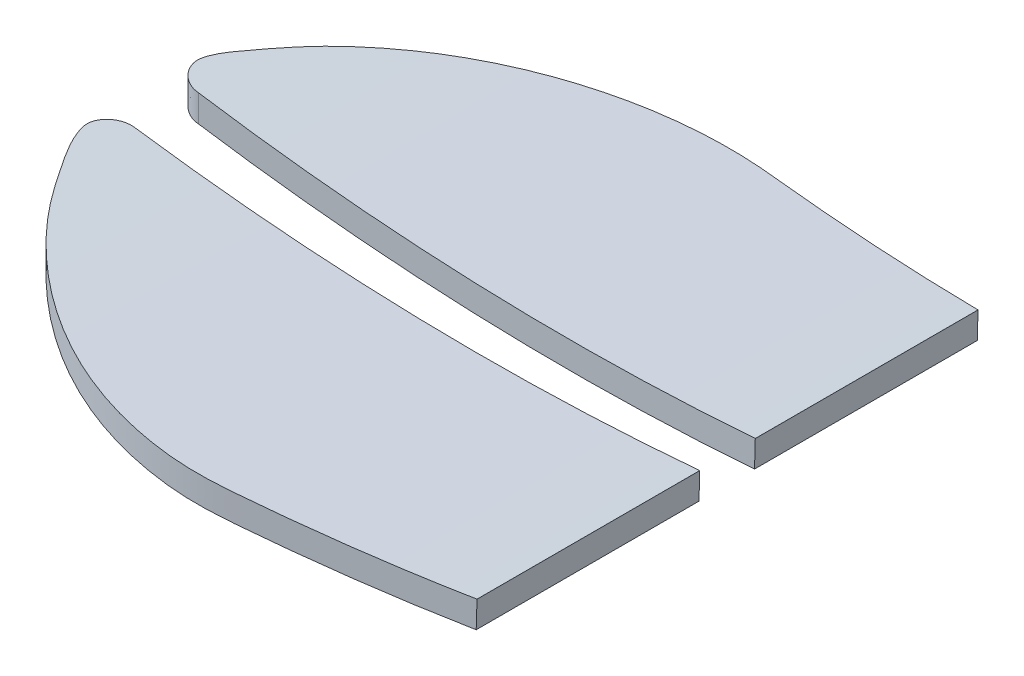
SolidWorks part; units mm, degrees
material "BUTİL"
ref_plane "Ön Düzlem" through (0, 0, 0) normal (0, 0, 1) x (1, 0, 0)
ref_plane "Üst Düzlem" through (0, 0, 0) normal (0, 1, 0) x (1, 0, 0)
ref_plane "Sağ Düzlem" through (0, 0, 0) normal (1, 0, 0) x (0, 0, -1)
sketch "Çizim1" plane through (0, 0, 0) normal (0, 0, 1) x (1, 0, 0)
  line L0 (-0.075, -2.7151) -> (0, -0.0079)
  line L1 (-59.4941, 2.233) -> (-59.4941, -0.5004)
  line L2 (0, -0.0079) -> (0, 0)
  arc A0 (-59.4941, 2.233) -> (0, 0) centre (-20.465, 248.4228) ccw
  arc A1 (-59.4941, -0.5004) -> (-0.075, -2.7151) centre (-20.465, 248.4228) ccw
extrude "Yükseklik-Ekstrüzyon1" add sketch "Çizim1" along normal mid plane 110
sketch "Çizim5" plane through (0, 0, 0) normal (0, 1, 0) x (1, 0, 0)
  line L0 (-56.3678, 4.1753) -> (0, 4.1753)
  line L1 (0, 0.1753) -> (-56.3678, 0.1753)
  line L2 (-21.7191, -27.214) -> (0, -25.541)
  line L3 (0, 0.1753) -> (0, -25.541)
  line L5 (0, 29.8916) -> (-21.7191, 31.5645)
  line L6 (0, 29.8916) -> (0, 4.1753)
  arc A1 (-56.3678, 0.1753) -> (-59.2571, -4.1448) centre (-56.3678, -2.951) ccw
  arc A2 (-59.2571, -4.1448) -> (-21.7191, -27.214) centre (-24.599, 10.1753) ccw
  arc A6 (-21.7191, 31.5645) -> (-59.2571, 8.4954) centre (-24.599, -5.8247) ccw
  arc A7 (-59.2571, 8.4954) -> (-56.3678, 4.1753) centre (-56.3678, 7.3016) ccw
extrude "Kes-Ekstrüzyon1" cut sketch "Çizim5" along normal blind 110 and the other way blind 110 flip side to cut
sketch "Çizim6" plane through (726.7394, 65.4586, 18.9231) normal (-0.0019, 1, 0) x (1, 0.0019, -0.0003)
  line L0 (-726.8539, 23.3444) -> (-726.8452, 49.0607) construction
  line L1 (-696.2248, 43.7824) -> (-746.7612, 48.5613) construction
  line L2 (-746.7612, 48.5613) -> (-749.9433, 48.8623) construction
  line L3 (-783.4317, 24.5417) -> (-726.4431, 24.1843)
  line L4 (-746.7694, 24.3118) -> (-713.9224, 24.1058) construction
  line L5 (-726.4432, 23.9445) -> (-726.4357, 46.177) construction
  line L6 (-726.4431, 24.1843) -> (-726.4431, 21.898)
  line L7 (-726.4431, 21.898) -> (-791.0567, 21.898)
  line L8 (-791.0567, 21.898) -> (-785.7198, 49.9742)
  line L9 (-785.7198, 49.9742) -> (-751.8286, 55.5551)
  line L10 (-751.8286, 55.5551) -> (-721.174, 52.7647)
  line L11 (-721.174, 52.7647) -> (-719.2329, 52.7647)
  line L12 (-726.846, 46.6781) -> (-719.2329, 52.7647)
  line L13 (-746.7796, -5.782) -> (-696.24, -1.0373) construction
  line L14 (-749.9619, -6.0808) -> (-746.7796, -5.782) construction
  line L15 (-783.4338, 18.2625) -> (-726.203, 18.5826)
  line L16 (-713.9242, 18.6513) -> (-746.7714, 18.4676) construction
  line L17 (-726.203, 18.5826) -> (-726.203, 20.675)
  line L18 (-726.203, 20.675) -> (-791.0567, 20.675)
  line L19 (-791.0567, 20.675) -> (-791.0567, -3.2755)
  line L20 (-791.0567, -3.2755) -> (-754.8184, -12.401)
  line L21 (-754.8184, -12.401) -> (-721.9035, -11.4723)
  line L22 (-721.9035, -11.4723) -> (-726.7955, -3.9059)
  spline S0 degree 3 poles (-726.846, 46.6781) (-728.9177, 46.8738) (-733.0096, 47.2614) (-738.7557, 47.8029) (-743.7553, 48.2808) (-747.6567, 48.6366) (-751.4705, 49.0369) (-755.4277, 49.0541) (-759.8139, 48.5036) (-764.6206, 47.3078) (-769.3937, 45.3369) (-773.7186, 42.6856) (-777.0614, 40.018) (-779.6661, 37.4064) (-782.2481, 34.2829) (-784.1295, 31.1758) (-785.6449, 28.5796) (-786.2484, 26.0304) (-784.7201, 24.4666) (-783.4317, 24.5417) knots 0 0 0 0 0.086439 0.170735 0.239744 0.295063 0.333475 0.399005 0.458901 0.516649 0.60434 0.672158 0.726745 0.781614 0.8251 0.894754 0.932114 0.949969 1 1 1 1
  spline S1 degree 3 poles (-749.9433, 48.8623) (-751.7958, 49.0374) (-753.6368, 49.0658) (-757.2967, 48.8418) (-759.1156, 48.5894) (-761.3751, 48.0934) (-761.8273, 47.9848) (-762.7235, 47.751) (-763.1679, 47.6257) (-764.4903, 47.2252) (-765.3573, 46.9252) (-767.9157, 45.9285) (-769.5646, 45.1354) (-771.9522, 43.7494) (-772.7369, 43.2522) (-774.2546, 42.2054) (-774.9889, 41.6555) (-777.1206, 39.9275) (-778.4469, 38.6719) (-780.2933, 36.6313) (-780.8853, 35.9241) (-782.0177, 34.4582) (-782.553, 33.7063) (-784.0672, 31.3947) (-784.9555, 29.7792) (-785.7198, 28.0874) knots 0 0 0 0 0.125 0.125 0.25 0.25 0.28125 0.28125 0.3125 0.3125 0.375 0.375 0.5 0.5 0.5625 0.5625 0.625 0.625 0.75 0.75 0.8125 0.8125 0.875 0.875 1 1 1 1 construction
  spline S2 degree 3 poles (-785.9392, 26.9242) (-785.933, 26.803) (-785.918, 26.6825) (-785.8617, 26.4001) (-785.8129, 26.2402) (-785.6866, 25.9367) (-785.6084, 25.7908) (-785.4235, 25.5154) (-785.319, 25.389) (-785.0869, 25.1579) (-784.9576, 25.0523) (-784.6846, 24.8708) (-784.5407, 24.7942) (-784.2379, 24.6692) (-784.0789, 24.6212) (-783.7591, 24.5579) (-783.5967, 24.5417) (-783.4317, 24.5417) knots 0.032863 0.032863 0.032863 0.032863 0.125 0.125 0.25 0.25 0.375 0.375 0.5 0.5 0.625 0.625 0.75 0.75 0.875 0.875 1 1 1 1 construction
  spline S3 degree 3 poles (-726.7955, -3.9059) (-727.9241, -4.0118) (-729.6956, -4.1781) (-732.4726, -4.4388) (-735.0275, -4.6787) (-738.1167, -4.9687) (-741.5515, -5.2912) (-745.0601, -5.6205) (-748.7891, -5.971) (-753.0459, -6.3679) (-758.742, -6.0063) (-764.9634, -4.4934) (-770.8502, -1.8008) (-776.3831, 1.9916) (-780.8323, 6.4511) (-783.8335, 11.0723) (-785.5268, 13.867) (-786.2751, 16.7092) (-784.7872, 18.3319) (-783.4338, 18.2625) knots 0 0 0 0 0.047075 0.073895 0.115832 0.153643 0.202749 0.259105 0.299979 0.358332 0.43643 0.535803 0.622505 0.703757 0.813444 0.881169 0.932322 0.948856 1 1 1 1
  spline S4 degree 3 poles (-785.7243, 14.7183) (-784.961, 13.0257) (-784.0768, 11.4162) (-782.0772, 8.3552) (-780.9618, 6.9038) (-779.4189, 5.1906) (-779.1021, 4.8524) (-778.4571, 4.1899) (-778.1291, 3.866) (-777.1291, 2.916) (-776.441, 2.3113) (-774.3136, 0.582) (-772.8115, -0.4586) (-770.8268, -1.617) (-770.4244, -1.8415) (-769.6088, -2.276) (-769.1949, -2.4862) (-767.9472, -3.0896) (-767.1044, -3.4573) (-764.5437, -4.459) (-762.7936, -4.9925) (-760.1032, -5.5898) (-759.1954, -5.755) (-757.3574, -6.0152) (-756.4333, -6.1093) (-753.6641, -6.2826) (-751.8147, -6.2547) (-749.9619, -6.0808) knots 0 0 0 0 0.125 0.125 0.25 0.25 0.28125 0.28125 0.3125 0.3125 0.375 0.375 0.5 0.5 0.53125 0.53125 0.5625 0.5625 0.625 0.625 0.75 0.75 0.8125 0.8125 0.875 0.875 1 1 1 1 construction
  spline S5 degree 3 poles (-783.4338, 18.2625) (-783.5989, 18.2625) (-783.7612, 18.2465) (-784.0807, 18.1834) (-784.2394, 18.1357) (-784.5429, 18.0107) (-784.6869, 17.9342) (-784.9597, 17.7532) (-785.0892, 17.6476) (-785.3217, 17.4164) (-785.4261, 17.2902) (-785.6107, 17.016) (-785.6897, 16.869) (-785.8161, 16.5657) (-785.8647, 16.4073) (-785.9215, 16.1236) (-785.9366, 16.0028) (-785.9429, 15.8816) knots 0 0 0 0 0.125 0.125 0.25 0.25 0.375 0.375 0.5 0.5 0.625 0.625 0.75 0.75 0.875 0.875 0.967105 0.967105 0.967105 0.967105 construction
extrude "Kes-Ekstrüzyon2" cut sketch "Çizim6" against normal blind 85
